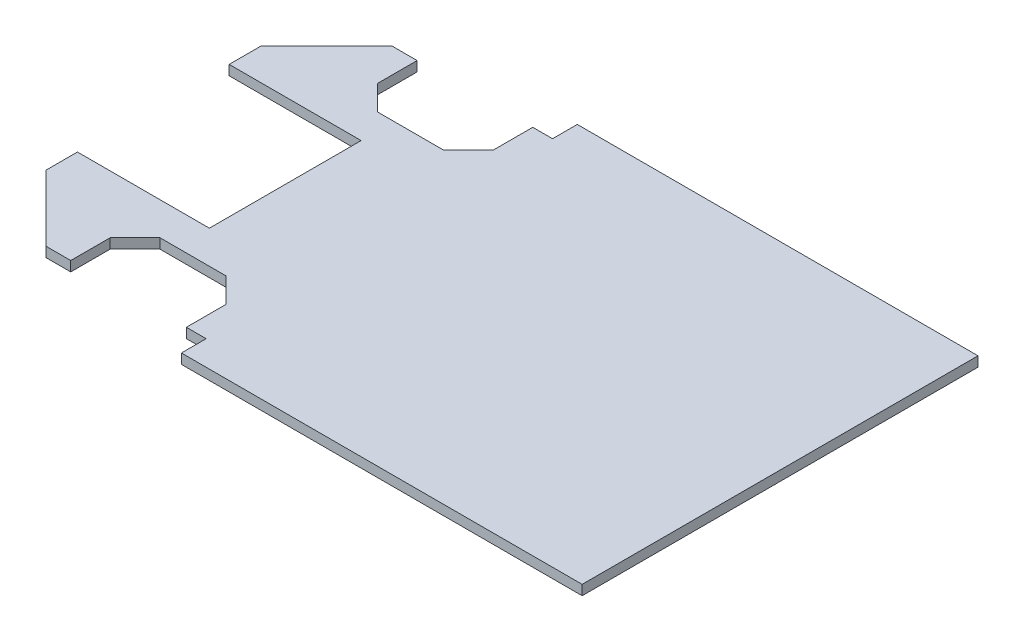
SolidWorks part; units mm, degrees
ref_plane "Front Plane" through (0, 0, 0) normal (0, 0, 1) x (1, 0, 0)
ref_plane "Top Plane" through (0, 0, 0) normal (0, 1, 0) x (1, 0, 0)
ref_plane "Right Plane" through (0, 0, 0) normal (1, 0, 0) x (0, 0, -1)
sketch "Sketch1" plane through (0, 0, 0) normal (0, 1, 0) x (1, 0, 0)
  line L0 (190, 0) -> (0, 0) construction
  line L1 (0, -60) -> (190, -60)
  line L2 (0, -60) -> (0, 60)
  line L3 (0, 60) -> (190, 60)
  line L4 (190, -60) -> (190, 60)
  line L5 (0, -32.5266) -> (19.9734, -52.5)
  line L6 (40, 23) -> (0, 23)
  line L7 (40, 23) -> (40, -23)
  line L8 (40, -23) -> (0, -23)
  line L9 (0, 23) -> (0, -23)
  line L10 (40, 23) -> (0, -23) construction
  line L11 (40, -23) -> (0, 23) construction
  line L12 (19.9734, -52.5) -> (27.4734, -52.5)
  line L13 (68.5266, -52.5) -> (68.5266, -60)
  line L14 (35, -33) -> (27.4734, -40.5266)
  line L15 (27.4734, -52.5) -> (27.4734, -40.5266) construction
  line L16 (27.4734, -40.5266) -> (27.4734, -52.5)
  line L18 (35, -33) -> (55, -33)
  line L19 (55, -33) -> (62.5266, -40.5266)
  line L20 (62.5266, -52.5) -> (68.5266, -52.5)
  line L21 (47.5, -37) -> (42.5, -37) construction
  line L22 (45, -37) -> (45, -33) construction
  line L23 (45, -56.5) -> (45, -52.5) construction
  line L24 (39.4, -56.5) -> (50.6, -56.5) construction
  line L25 (27.4734, -52.5) -> (62.5266, -52.5) construction
  line L27 (62.5266, -40.5266) -> (62.5266, -52.5)
  line L28 (68.5266, 52.5) -> (68.5266, 60)
  line L29 (62.5266, 52.5) -> (68.5266, 52.5)
  line L31 (62.5266, 40.5266) -> (62.5266, 52.5)
  line L32 (55, 33) -> (62.5266, 40.5266)
  line L33 (35, 33) -> (55, 33)
  line L34 (35, 33) -> (27.4734, 40.5266)
  line L35 (27.4734, 40.5266) -> (27.4734, 52.5)
  line L36 (19.9734, 52.5) -> (27.4734, 52.5)
  line L37 (0, 32.5266) -> (19.9734, 52.5)
  point P7 (0, 0)
  point P8 (20, 0)
  point P34 (63.1457, -41.1457)
  point P35 (0, 0)
  point P45 (20, -52.5)
  dimension "D1" = 120
  dimension "D2" = 190
  dimension "D3" = 40
  dimension "D4" = 23
  dimension "D5" = 10
  dimension "D6" = 20
  dimension "D7" = 45
  dimension "D8" = 45
  dimension "D9" = 135
  dimension "D10" = 7.5
  dimension "D11" = 6
extrude "Boss-Extrude1" add sketch "Sketch1" along normal blind 3 contours L7 L8 L2 L1 L4 L3 L6 region at (111.3224, 0, 0)
